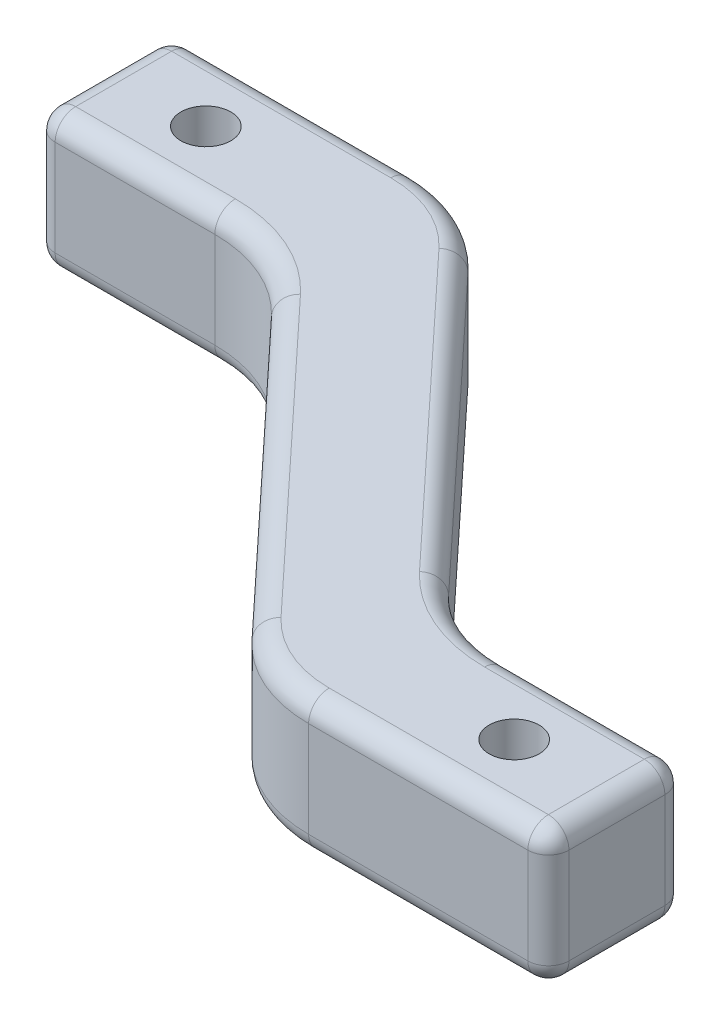
SolidWorks part; units mm, degrees
ref_plane "Alzado" through (0, 0, 0) normal (0, 0, 1) x (1, 0, 0)
ref_plane "Planta" through (0, 0, 0) normal (0, 1, 0) x (1, 0, 0)
ref_plane "Vista lateral" through (0, 0, 0) normal (1, 0, 0) x (0, 0, -1)
sketch "Croquis1" plane through (0, 0, 0) normal (0, 1, 0) x (1, 0, 0)
  line L0 (-65, 0) -> (65, 0) construction
  line L1 (-65, 0) -> (-21.3058, 0)
  line L2 (-21.3058, 0) -> (30, -55)
  line L3 (30, -55) -> (65, -55)
  line L4 (65, -55) -> (65, -75)
  line L5 (65, -75) -> (21.3058, -75)
  line L6 (21.3058, -75) -> (-30, -20)
  line L7 (-30, -20) -> (-65, -20)
  line L8 (-65, -20) -> (-65, 0)
  line L9 (-65, -10) -> (-50, -10) construction
  line L10 (50, -65) -> (65, -65) construction
  circle A0 centre (-50, -10) radius 3.65
  circle A1 centre (50, -65) radius 3.65
  point P0 (-65, -10)
  point P4 (0, 0)
  point P13 (65, -65)
  dimension "D8" = 7.3
  dimension "D1" = 130
  dimension "D2" = 20
  dimension "D3" = 35
  dimension "D4" = 55
  dimension "D5" = 20
  dimension "D6" = 15
  dimension "D7" = 15
extrude "Saliente-Extruir1" add sketch "Croquis1" along normal blind 20
fillet "Redondeo1" radius 20 4 edges at (21.3058, 10, 75) (30, 10, 55) (-21.3058, 10, 0) (-30, 10, 20)
sketch "Croquis3" plane through (0, 20, 0) normal (0, 1, 0) x (1, 0, 0)
  line L5 (65, -52.5479) -> (45, -52.5479)
  line L6 (45, -52.5479) -> (45, -75)
  line L7 (45, -75) -> (65, -75)
  line L8 (65, -75) -> (65, -52.5479)
  line L9 (30, -75) -> (65, -75) construction
  dimension "D2" = 20
extrude "Cortar-Extruir2" [suppressed] cut sketch "Croquis3" against normal blind 10
sketch "Croquis5" plane through (0, 0, 0) normal (0, -1, 0) x (1, 0, 0)
  line L0 (-65, 0) -> (-45, 0)
  line L1 (-45, 0) -> (-45, 24.0911)
  line L2 (-45, 24.0911) -> (-65, 24.0911)
  line L3 (-65, 24.0911) -> (-65, 0)
  dimension "D1" = 20
extrude "Cortar-Extruir3" [suppressed] cut sketch "Croquis5" against normal blind 10
fillet "Redondeo2" radius 3 28 edges at (-4.3471, 0, 47.5) (-30.7208, 0, 21.6581) (4.3471, 0, 27.5) (22.0266, 0, 73.3419) (-4.3471, 20, 47.5) (-30.7208, 20, 21.6581) (-51.8471, 0, 20) (-22.0266, 0, 1.6581) (30.7208, 0, 53.3419) (47.5, 0, 75) (22.0266, 20, 73.3419) (-65, 10, 20) (-51.8471, 20, 20) (-65, 0, 10) (-47.5, 0, 0) (51.8471, 0, 55) (65, 0, 65) (65, 10, 75) (47.5, 20, 75) (-65, 20, 10) (-65, 10, 0) (65, 10, 55) (65, 20, 65) (-47.5, 20, 0) (51.8471, 20, 55) (-22.0266, 20, 1.6581) (30.7208, 20, 53.3419) (4.3471, 20, 27.5)
